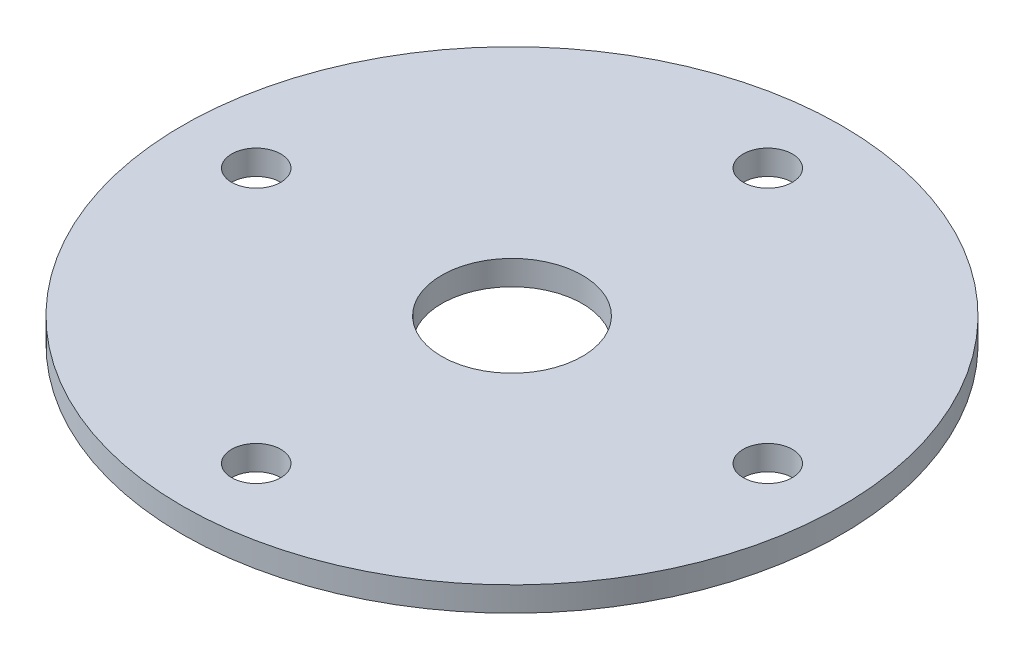
SolidWorks part; units mm, degrees
ref_plane "Front Plane" through (0, 0, 0) normal (0, 0, 1) x (1, 0, 0)
ref_plane "Top Plane" through (0, 0, 0) normal (0, 1, 0) x (1, 0, 0)
ref_plane "Right Plane" through (0, 0, 0) normal (1, 0, 0) x (0, 0, -1)
sketch "Sketch1" plane through (0, 0, 0) normal (0, 1, 0) x (1, 0, 0)
  line L0 (0, 52) -> (0, -52)
  circle A0 centre (0, 0) radius 52 construction
  circle A1 centre (0, 0) radius 67
  circle A2 centre (0, 52) radius 5
  circle A3 centre (52, 0) radius 5
  circle A4 centre (0, -52) radius 5
  circle A5 centre (-52, 0) radius 5
  point P7 (0, 0)
  point P8 (0, 0)
  point P15 (0, 0)
  point P16 (-65.652, 5.6867)
  point P17 (0, 0)
  dimension "D1" = 104
  dimension "D2" = 134
  dimension "D3" = 10
  dimension "D4" = 4
extrude "Boss-Extrude1" add sketch "Sketch1" along normal blind 5 contours A1 A5 A4 A2 A3 region at (-65.105, 0, 0)
sketch "Sketch2" plane through (0, 5, 0) normal (0, 1, 0) x (1, 0, 0)
  circle A0 centre (0, 0) radius 14.3
  circle A1 centre (0, 0) radius 19.3
  point P4 (0, 0)
  dimension "D1" = 28.6
  dimension "D2" = 38.6
extrude "Boss-Extrude2" [suppressed] add sketch "Sketch2" along normal blind 40 contours A1 | A0
sketch "Sketch4" [suppressed] plane through (0, 0, 0) normal (0, 0, 1) x (1, 0, 0)
  line L0 (0, 45) -> (0, 5) construction
  line L1 (19.3, 45) -> (-19.3, 45) construction
  line L2 (19.3, 5) -> (-19.3, 5) construction
  circle A0 centre (0, 25) radius 5
  point P8 (0, 0)
  dimension "D1" = 10
  dimension "D2" = 20
extrude "Cut-Extrude2" [suppressed] cut sketch "Sketch4" against normal through all both and the other way through all contours A0
fillet "Fillet1" [suppressed] radius 10
extrude "Cut-Extrude3" cut sketch "Sketch2<4>" against normal through all both and the other way through all contours A0
sketch "Sketch2<4>" plane through (0, 5, 0) normal (0, 1, 0) x (1, 0, 0) same geometry as "Sketch2"
equation "\"bcd\"= 104"
equation "\"boltholedim\"= 10"
equation "\"teethnumber\"= 4"
equation "\"D1@Sketch1\"=\"bcd\""
equation "\"D2@Sketch1\"=\"bcd\"+30"
equation "\"D2@Sketch2\"=\"D1@Sketch2\"+10"
equation "\"D1@Sketch4\"=\"boltholedim\""
